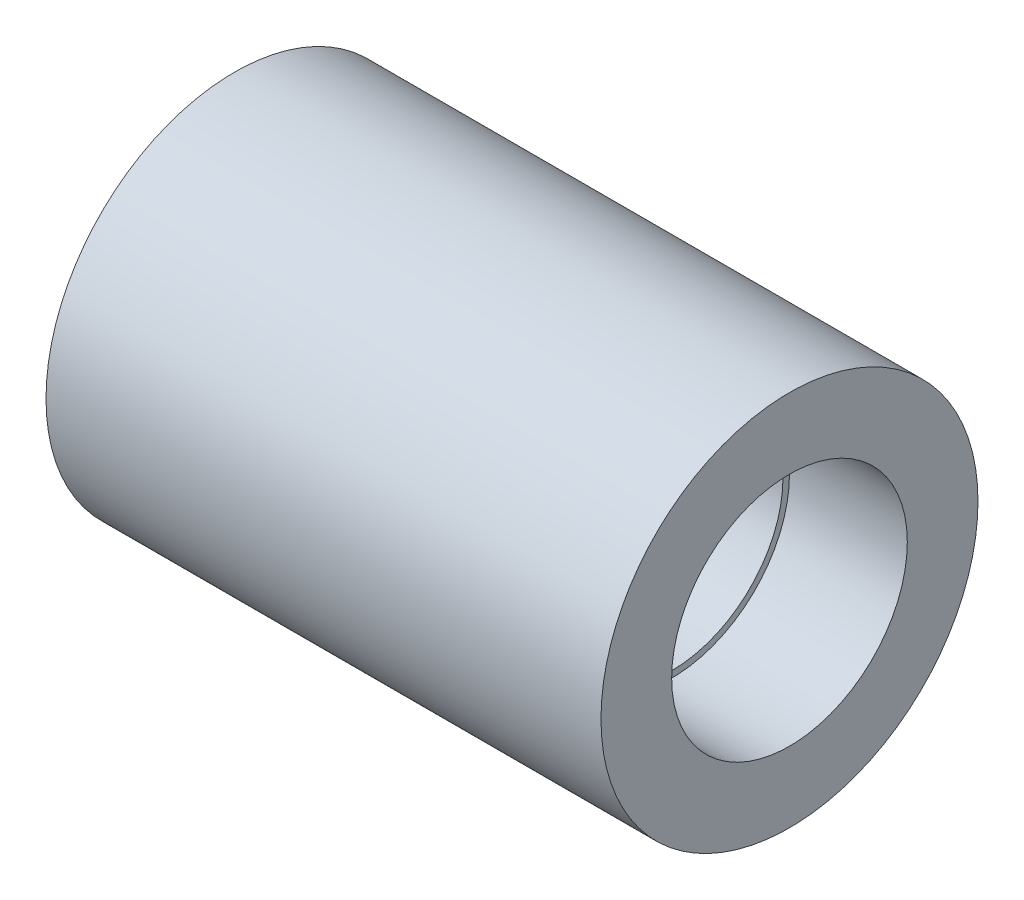
SolidWorks part; units mm, degrees
material "PLA"
ref_plane "Front Plane" through (0, 0, 0) normal (0, 0, 1) x (1, 0, 0)
ref_plane "Top Plane" through (0, 0, 0) normal (0, 1, 0) x (1, 0, 0)
ref_plane "Right Plane" through (0, 0, 0) normal (1, 0, 0) x (0, 0, -1)
sketch "Sketch1" plane through (0, 0, 0) normal (1, 0, 0) x (0, 0, -1)
  circle A0 centre (0, 0) radius 3.175
  circle A1 centre (0, 0) radius 5.08
  circle A2 centre (0, 0) radius 3
  dimension "D1" = 6.35
  dimension "D2" = 10.16
  dimension "D3" = 6
extrude "Boss-Extrude1" add sketch "Sketch1" along normal blind 3.175 contours A1 A0 region at (0, 0, 4.9363)
extrude "Boss-Extrude2" add sketch "Sketch1<3>" against normal blind 11.78 contours A0 A2 | A1 A0 region at (0, 0, 3.0852) region at (0, 0, 4.9363)
sketch "Sketch1<3>" plane through (0, 0, 0) normal (1, 0, 0) x (0, 0, -1) same geometry as "Sketch1"
